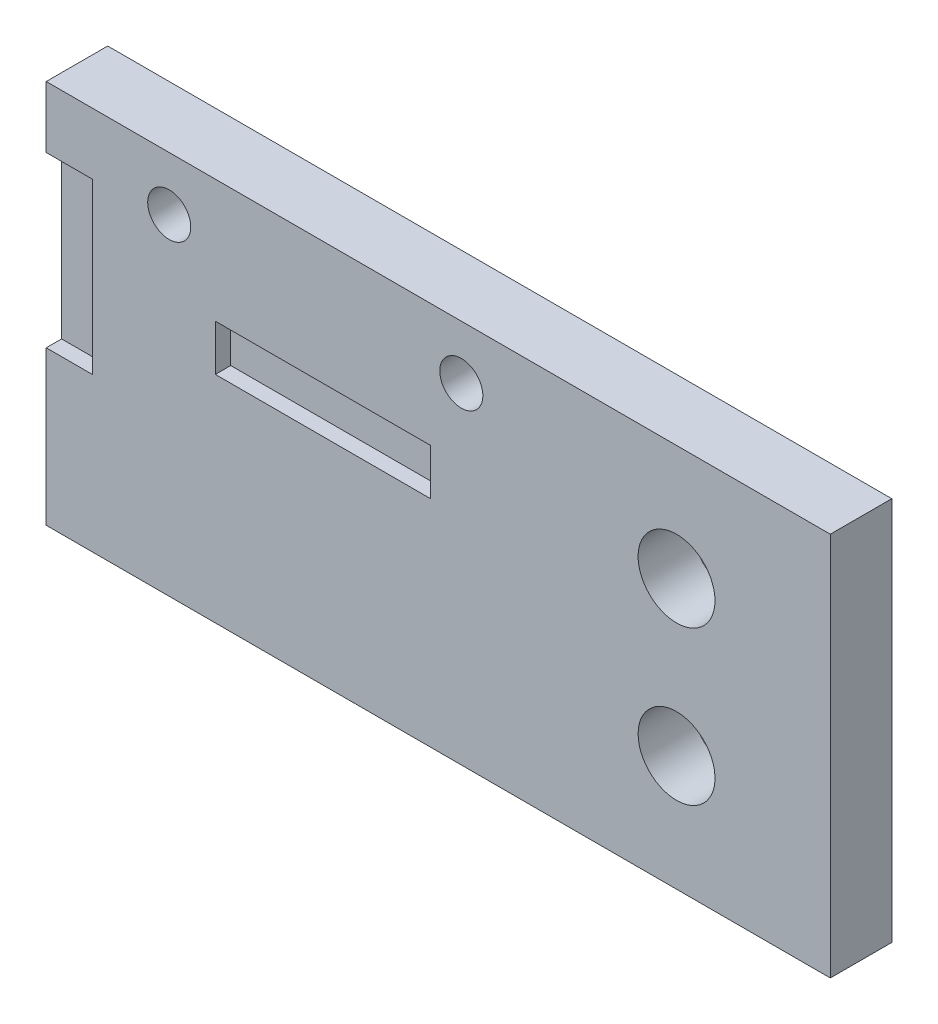
SolidWorks part; units mm, degrees
ref_plane "Front Plane" through (0, 0, 0) normal (0, 0, 1) x (1, 0, 0)
ref_plane "Top Plane" through (0, 0, 0) normal (0, 1, 0) x (1, 0, 0)
ref_plane "Right Plane" through (0, 0, 0) normal (1, 0, 0) x (0, 0, -1)
sketch "Sketch1" plane through (0, 0, 0) normal (0, 0, 1) x (1, 0, 0)
  line L1 (-20, -12.5) -> (20, -12.5)
  line L2 (-20, -12.5) -> (-20, 12.5)
  line L3 (-20, 12.5) -> (20, 12.5)
  line L4 (20, -12.5) -> (20, 12.5)
  line L5 (-20, -12.5) -> (20, 12.5) construction
  line L6 (-20, 12.5) -> (20, -12.5) construction
  point P0 (0, 0)
extrude "Boss-Extrude1" add sketch "Sketch1" along normal blind 4
sketch "Sketch3" plane through (0, 0, 0) normal (0, 0, 1) x (1, 0, 0)
  line L0 (20, 4.5) -> (0, 4.5) construction
  line L1 (20, -12.5) -> (20, 12.5) construction
  line L2 (20, 12.5) -> (20, 4.5) construction
  line L3 (20, 12.5) -> (-20, 12.5) construction
  line L4 (-20, 12.5) -> (-20, 8.5) construction
  line L5 (0, 4.5) -> (14, 4.5)
  line L6 (0, 4.5) -> (0, 1.5)
  line L7 (0, 1.5) -> (14, 1.5)
  line L8 (14, 4.5) -> (14, 1.5)
  line L9 (0, 4.5) -> (0, 12.5) construction
  line L10 (-20, 12.5) -> (-20, -12.5) construction
  line L11 (-20, 8.5) -> (-11, 8.5) construction
  line L12 (20, 12.5) -> (-20, 12.5) construction
  line L13 (-11, 8.5) -> (-8, 8.5)
  line L14 (-11, 8.5) -> (-11, -2.5)
  line L15 (-11, -2.5) -> (-8, -2.5)
  line L16 (-8, 8.5) -> (-8, -2.5)
extrude "Cut-Extrude1" cut sketch "Sketch3" against normal blind 1 from surface starting at face at (0, 0, 4)
sketch "Sketch4" plane through (0, 0, 0) normal (0, 0, 1) x (1, 0, 0)
  line L0 (20, 12.5) -> (16, 12.5) construction
  line L1 (20, 12.5) -> (-20, 12.5) construction
  line L2 (16, 12.5) -> (16, 9) construction
  line L3 (16, 9) -> (-3, 9) construction
  circle A0 centre (16, 9) radius 1.4
  circle A1 centre (-3, 9) radius 1.4
extrude "Cut-Extrude2" cut sketch "Sketch4" along normal blind 11
sketch "Sketch7" plane through (0, 0, 0) normal (0, 0, 1) x (1, 0, 0)
  line L0 (-20, -12.5) -> (20, -12.5) construction
  line L1 (-20, 12.5) -> (-11, 12.5)
  line L2 (-20, 12.5) -> (-20, -12.5)
  line L3 (-20, -12.5) -> (-11, -12.5)
  line L4 (-11, 12.5) -> (-11, -12.5)
extrude "Cut-Extrude5" cut sketch "Sketch7" along normal blind 21
sketch "Sketch8" plane through (0, 0, 0) normal (0, 0, 1) x (1, 0, 0)
  line L1 (20, 12.5) -> (40, 12.5)
  line L2 (20, 12.5) -> (20, -12.5)
  line L3 (20, -12.5) -> (40, -12.5)
  line L4 (40, 12.5) -> (40, -12.5)
extrude "Boss-Extrude2" add sketch "Sketch8" along normal blind 4
sketch "Sketch9" plane through (0, 0, 0) normal (0, 0, 1) x (1, 0, 0)
  circle A0 centre (30, 5) radius 2.5
  circle A1 centre (30, -4.9935) radius 2.5
extrude "Cut-Extrude6" cut sketch "Sketch9" along normal through all
sketch "Sketch10" plane through (0, 0, 0) normal (0, 0, 1) x (1, 0, 0)
  line L2 (27.5, -0.6634) -> (27.5, 0.6699)
  line L3 (32.5, 0) -> (32.5, -0.6634)
  line L4 (32.5, 0) -> (32.5, 0.6699)
  arc A0 (32.5, 0.6699) -> (27.5, 0.6699) centre (30, 5) ccw
  arc A1 (27.5, -0.6634) -> (32.5, -0.6634) centre (30, -4.9935) ccw
extrude "Cut-Extrude7" cut sketch "Sketch10" along normal blind 0.5
fillet "Fillet3" radius 1 4 edges at (27.5, -0.6634, 0.25) (27.5, 0.6699, 0.25) (32.5, -0.6634, 0.25) (32.5, 0.6699, 0.25)
